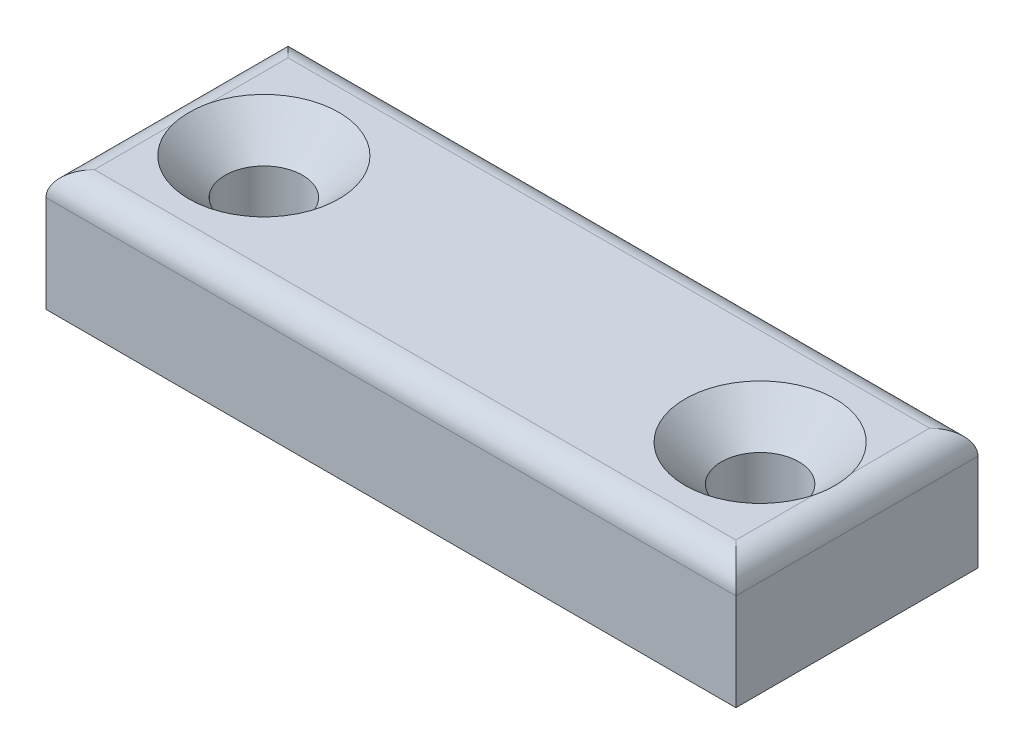
SolidWorks part; units mm, degrees
material "PLA Black"
ref_plane "Front Plane" through (0, 0, 0) normal (0, 0, 1) x (1, 0, 0)
ref_plane "Top Plane" through (0, 0, 0) normal (0, 1, 0) x (1, 0, 0)
ref_plane "Right Plane" through (0, 0, 0) normal (1, 0, 0) x (0, 0, -1)
sketch "Sketch1" plane through (0, 0, 0) normal (0, 1, 0) x (1, 0, 0)
  line L0 (-28.5, 5) -> (1.6981, 5) construction
  line L1 (0, 0) -> (-28.5, 0)
  line L2 (0, 0) -> (0, 10)
  line L3 (0, 10) -> (-28.5, 10)
  line L4 (-28.5, 0) -> (-28.5, 10)
  circle A0 centre (-4, 5) radius 1.6
  circle A1 centre (-24.5, 5) radius 1.6
  dimension "D3" = 3.2
  dimension "3.2" = 3.2
  dimension "D1" = 28.5
  dimension "D2" = 10
  dimension "D5" = 4
  dimension "D6" = 4
extrude "Boss-Extrude1" add sketch "Sketch1" along normal blind 5
fillet "Fillet1" radius 1 4 edges at (-14.25, 5, -10) (-14.25, 5, 0) (-28.5, 5, -5) (0, 5, -5)
chamfer "Chamfer1" distance 1.5 angle 45 2 edges at (-24.5, 5, -3.4) (-4, 5, -3.4)
